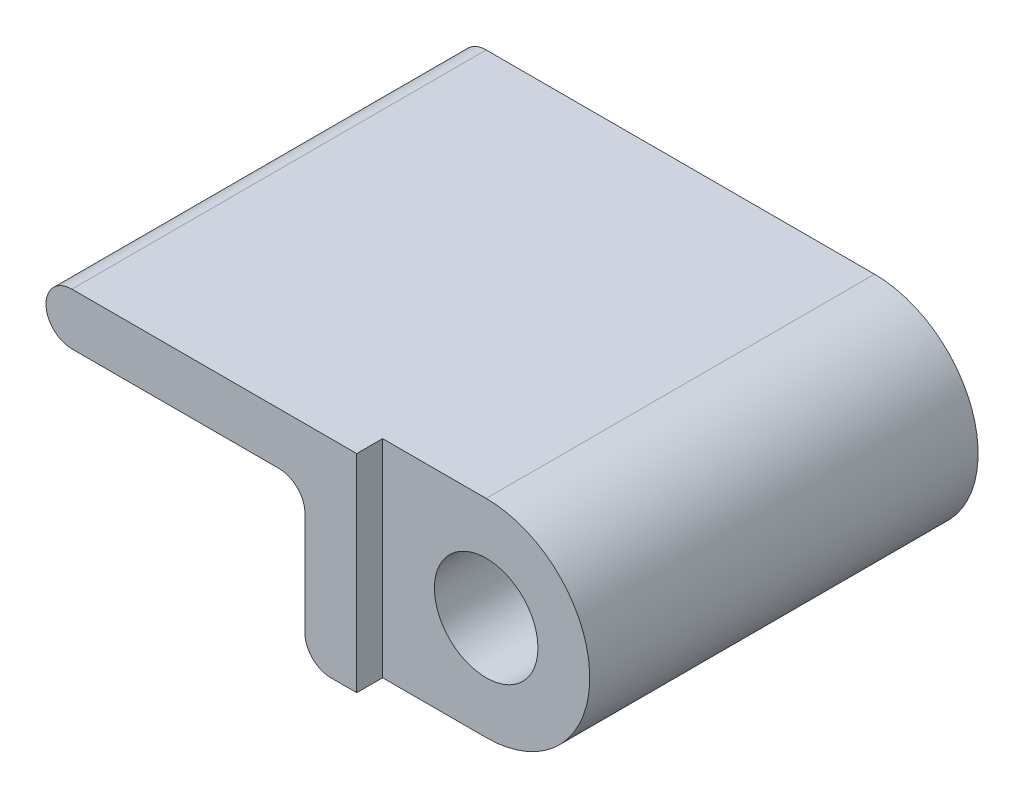
SolidWorks part; units mm, degrees
material "ABS"
ref_plane "Front Plane" through (0, 0, 0) normal (0, 0, 1) x (1, 0, 0)
ref_plane "Top Plane" through (0, 0, 0) normal (0, 1, 0) x (1, 0, 0)
ref_plane "Right Plane" through (0, 0, 0) normal (1, 0, 0) x (0, 0, -1)
sketch "Sketch1" plane through (0, 0, 0) normal (0, 0, 1) x (1, 0, 0)
  line L0 (-6.35, 0) -> (-6.35, 3.175)
  line L1 (0, 3.175) -> (-25.4, 3.175)
  line L2 (-25.4, 3.175) -> (-25.4, 6.35)
  line L3 (-25.4, 6.35) -> (0, 6.35)
  line L4 (-6.35, -6.35) -> (0, -6.35)
  line L5 (-9.525, 3.175) -> (-6.35, 3.175)
  line L6 (-9.525, 3.175) -> (-9.525, -6.35)
  line L7 (-9.525, -6.35) -> (-6.35, -6.35)
  line L8 (-6.35, 3.175) -> (-6.35, -6.35)
  circle A0 centre (0, 0) radius 6.35
  circle A1 centre (0, 0) radius 3.175
  point P15 (-6.2008, 3.175)
  dimension "D1" = 6.35
  dimension "D2" = 12.7
  dimension "D3" = 25.4
extrude "Boss-Extrude1" add sketch "Sketch1" along normal blind 25.4 contours A0 L3 L2 L1 | A1 A0 | A0 L8 L3 | A0 L1 L0 | L8 L0 L1 L6 L7 | A0 L8 L4 region at (-7.9375, -1.5875, 0) region at (-4.9316, -4.9316, 0) region at (-5.9601, 1.597, 0) region at (-6.098, 2.3923, 0) region at (-14.613, 4.8143, 0)
sketch "Sketch2" plane through (0, 0, 25.4) normal (0, 0, 1) x (1, 0, 0)
  line L1 (6.35, -6.35) -> (-6.35, -6.35)
  line L2 (6.35, -6.35) -> (6.35, 6.35)
  line L3 (6.35, 6.35) -> (-6.35, 6.35)
  line L4 (-6.35, -6.35) -> (-6.35, 6.35)
  line L5 (6.35, -6.35) -> (-6.35, 6.35) construction
  line L6 (6.35, 6.35) -> (-6.35, -6.35) construction
  arc A0 (0, -6.35) -> (0, 6.35) centre (0, 0) ccw construction
  point P0 (0, 0)
  point P5 (-6.35, 4.8565)
  point P6 (0, 0)
extrude "Cut-Extrude1" cut sketch "Sketch2" against normal blind 1.5875
fillet "Fillet1" radius 1.5875 4 edges at (-9.525, 3.175, 12.7) (-9.525, -6.35, 12.7) (-25.4, 6.35, 12.7) (-25.4, 3.175, 12.7)
